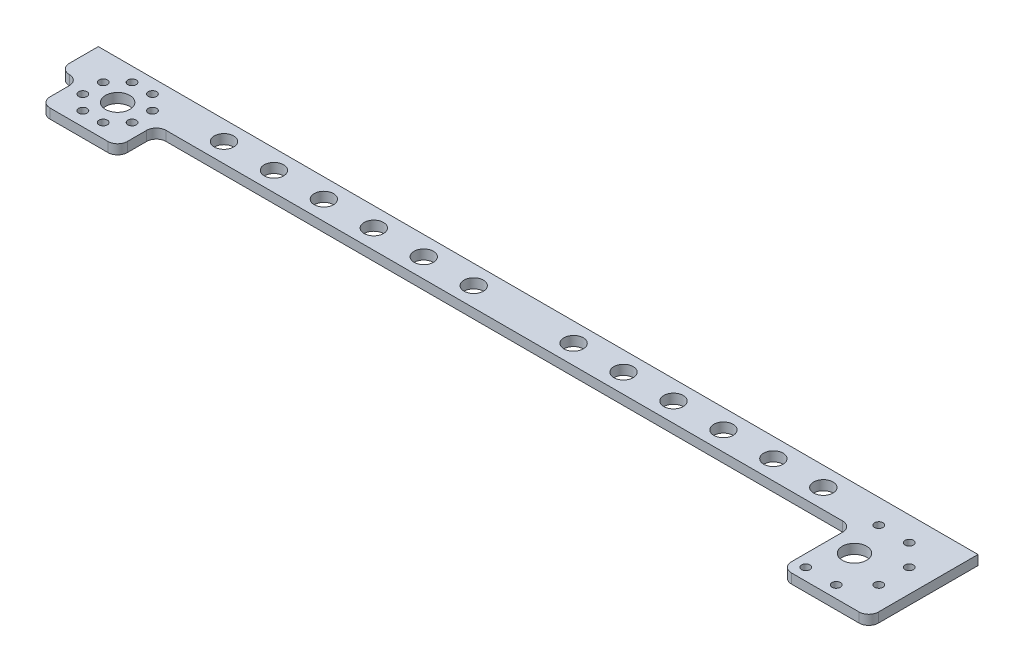
SolidWorks part; units mm, degrees
ref_plane "Front Plane" through (0, 0, 0) normal (0, 0, 1) x (1, 0, 0)
ref_plane "Top Plane" through (0, 0, 0) normal (0, 1, 0) x (1, 0, 0)
ref_plane "Right Plane" through (0, 0, 0) normal (1, 0, 0) x (0, 0, -1)
sketch "Sketch1" plane through (0, 0, 0) normal (0, 1, 0) x (1, 0, 0)
  line L1 (-228.6, 12.7) -> (228.6, 12.7)
  line L2 (-228.6, 12.7) -> (-228.6, -12.7) construction
  line L3 (-228.6, -12.7) -> (228.6, -12.7)
  line L4 (228.6, 12.7) -> (228.6, -12.7) construction
  line L5 (-228.6, 12.7) -> (228.6, -12.7) construction
  line L6 (-228.6, -12.7) -> (228.6, 12.7) construction
  line L7 (-228.6, 12.7) -> (-279.4, 12.7)
  line L8 (-279.4, 12.7) -> (-279.4, -38.1) construction
  line L9 (-279.4, -38.1) -> (-228.6, -38.1)
  line L10 (-228.6, -38.1) -> (-228.6, -12.7)
  line L11 (-279.4, 12.7) -> (-292.1, 12.7)
  line L12 (-292.1, 12.7) -> (-292.1, -12.7)
  line L13 (-292.1, -12.7) -> (-279.4, -12.7)
  line L14 (-279.4, -12.7) -> (-279.4, -38.1)
  line L15 (228.6, 12.7) -> (285.75, 12.7)
  line L16 (285.75, 12.7) -> (285.75, -59.055)
  line L17 (285.75, -59.055) -> (228.6, -59.055)
  line L18 (228.6, -59.055) -> (228.6, -12.7)
  point P0 (0, 0)
  dimension "D1" = 25.4
  dimension "D2" = 457.2
  dimension "D3" = 50.8
  dimension "D4" = 50.8
  dimension "D5" = 12.7
  dimension "D6" = 57.15
  dimension "D7" = 46.355
extrude "Boss-Extrude1" add sketch "Sketch1" along normal blind 6.35 contours L1 L15 L16 L17 L18 L3 L10 L9 L14 L13 L12 L11 L7
hole_wizard "M5 Clearance Hole1" positions "Sketch2" profile "Sketch3" hole size "M5" standard "ANSI Metric"
sketch "Sketch2" plane through (0, 6.35, 0) normal (0, 1, 0) x (1, 0, 0)
  line L0 (-279.4, -38.1) -> (-228.6, -38.1) construction
  line L15 (-270.1679, -19.397) -> (-270.1679, -6.003) construction
  line L16 (-270.1679, -6.003) -> (-260.697, 3.4679) construction
  line L17 (-260.697, 3.4679) -> (-247.303, 3.4679) construction
  line L18 (-247.303, 3.4679) -> (-237.8321, -6.003) construction
  line L19 (-237.8321, -6.003) -> (-237.8321, -19.397) construction
  line L20 (-237.8321, -19.397) -> (-247.303, -28.8679) construction
  line L21 (-247.303, -28.8679) -> (-260.697, -28.8679) construction
  line L22 (-260.697, -28.8679) -> (-270.1679, -19.397) construction
  circle A0 centre (-254, -12.7) radius 17.5 construction
  point P23 (-254, -38.1)
  point P37 (-260.697, -28.8679)
  point P41 (-237.8321, -19.397)
  point P67 (-260.697, 3.4679)
  point P69 (-247.303, 3.4679)
  point P71 (-237.8321, -6.003)
  point P84 (-270.1679, -19.397)
  point P107 (-247.303, -28.8679)
  point P110 (-270.1679, -6.003)
  dimension "D1" = 35
  dimension "D2" = 135
  dimension "D3" = 135
  dimension "D4" = 135
  dimension "D5" = 135
  dimension "D6" = 135
  dimension "D7" = 135
sketch "Sketch3" plane through (-270.1679, 6.35, 6.003) normal (1, 0, 0) x (0, 0, 1)
  line L0 (0, 0) -> (0, 14.3524)
  line L1 (0, 14.3524) -> (2.75, 12.7)
  line L2 (2.75, 12.7) -> (2.75, 0)
  line L5 (2.75, 0) -> (0, 0)
  line L10 (0, 14.3524) -> (-2.75, 12.7) construction
  line L11 (0, -6.35) -> (0, 107.95) construction
  dimension "Hole Dia." = 5.5
  dimension "Hole Depth" = 12.7
  dimension "Drill Angle" = 118
hole_wizard "#6 Clearance Hole2" positions "Sketch6" profile "Sketch7" hole size "#6" standard "ANSI Inch"
sketch "Sketch6" plane through (0, 0, -12.7) normal (0, 0, -1) x (-1, 0, 0)
  line L0 (215.9, 3.175) -> (-215.9, 3.175) construction
  line L2 (292.1, 0) -> (-285.75, 0) construction
  line L4 (292.1, 6.35) -> (292.1, 0) construction
  line L5 (-228.6, 6.35) -> (-228.6, 0) construction
  line L6 (-285.75, 6.35) -> (-285.75, 0) construction
  point P0 (279.4, 3.175)
  point P2 (215.9, 3.175)
  point P4 (0, 3.175)
  point P6 (-215.9, 3.175)
  point P14 (0, 3.175)
  point P26 (-276.225, 3.175)
  dimension "D1" = 3.175
  dimension "D2" = 12.7
  dimension "D3" = 12.7
  dimension "D4" = 12.7
  dimension "D5" = 9.525
sketch "Sketch7" plane through (-279.4, 3.175, -12.7) normal (1, 0, 0) x (0, 1, 0)
  line L0 (0, 0) -> (0, 13.8408)
  line L1 (0, 13.8408) -> (1.8986, 12.7)
  line L2 (1.8986, 12.7) -> (1.8986, 0)
  line L5 (1.8986, 0) -> (0, 0)
  line L10 (0, 13.8408) -> (-1.8986, 12.7) construction
  line L11 (0, -6.35) -> (0, 107.95) construction
  dimension "Hole Dia." = 3.7973
  dimension "Hole Depth" = 12.7
  dimension "Drill Angle" = 118
hole_wizard "M5 Clearance Hole2" positions "Sketch9" profile "Sketch10" hole size "M5" standard "ANSI Metric"
sketch "Sketch9" plane through (0, 6.35, 0) normal (0, 1, 0) x (1, 0, 0)
  line L1 (218.475, -17.175) -> (218.475, -37.175) construction
  line L3 (285.75, 12.7) -> (-292.1, 12.7) construction
  line L6 (228.6, -59.055) -> (228.6, -12.7) construction
  point P0 (218.475, -17.175)
  point P3 (218.475, -37.175)
  point P16 (244.475, -27.175)
  point P20 (256.475, -3.175)
  point P22 (256.475, -51.175)
  point P26 (236.475, -3.175)
  point P28 (236.475, -51.175)
  point P40 (218.475, -27.175)
  point P48 (270.475, -17.175)
  point P50 (270.475, -37.175)
  dimension "D1" = 15.875
  dimension "D2" = 20
  dimension "D3" = 15.875
  dimension "D4" = 26
  dimension "D5" = 8
  dimension "D6" = 24
  dimension "D7" = 48
  dimension "D8" = 20
  dimension "D9" = 26
sketch "Sketch10" plane through (218.475, 6.35, 17.175) normal (1, 0, 0) x (0, 0, 1)
  line L0 (0, 0) -> (0, 14.3524)
  line L1 (0, 14.3524) -> (2.75, 12.7)
  line L2 (2.75, 12.7) -> (2.75, 0)
  line L5 (2.75, 0) -> (0, 0)
  line L10 (0, 14.3524) -> (-2.75, 12.7) construction
  line L11 (0, -6.35) -> (0, 107.95) construction
  dimension "Hole Dia." = 5.5
  dimension "Hole Depth" = 12.7
  dimension "Drill Angle" = 118
fillet "Fillet1" radius 6.35 8 edges at (-228.6, 3.175, 38.1) (-228.6, 3.175, 12.7) (-292.1, 3.175, 12.7) (-279.4, 3.175, 38.1) (-279.4, 3.175, 12.7) (285.75, 3.175, 59.055) (228.6, 3.175, 59.055) (228.6, 3.175, 12.7)
sketch "Sketch8" plane through (0, 6.35, 0) normal (0, 1, 0) x (1, 0, 0)
  line L0 (285.75, 12.7) -> (-292.1, 12.7) construction
  line L1 (-196.85, 0) -> (-164.0417, 0) construction
  line L2 (-164.0417, 0) -> (-131.2333, 0) construction
  line L3 (-131.2333, 0) -> (-98.425, 0) construction
  line L4 (-98.425, 0) -> (-65.6167, 0) construction
  line L5 (-65.6167, 0) -> (-32.8083, 0) construction
  line L6 (-32.8083, 0) -> (0, 0) construction
  line L8 (-228.6, -31.75) -> (-228.6, -19.05) construction
  circle A0 centre (-254, -12.7) radius 8
  circle A1 centre (244.475, -27.175) radius 8
  circle A2 centre (-196.85, 0) radius 6.35 construction
  circle A3 centre (-164.0417, 0) radius 6.35 construction
  circle A4 centre (-131.2333, 0) radius 6.35 construction
  circle A5 centre (-65.6167, 0) radius 6.35 construction
  circle A6 centre (-32.8083, 0) radius 6.35 construction
  circle A7 centre (-98.425, 0) radius 6.35 construction
  dimension "D1" = 16
  dimension "D2" = 16
  dimension "D4" = 12.7
  dimension "D3" = 12.7
  dimension "D5" = 31.75
  dimension "D6" = 228.6
extrude "Cut-Extrude1" cut sketch "Sketch8" against normal blind 6.35
sketch "Sketch11" plane through (0, 6.35, 0) normal (0, 1, 0) x (1, 0, 0)
  circle A0 centre (-196.85, 0) radius 6.35
  circle A1 centre (-164.0417, 0) radius 6.35
  circle A2 centre (-131.2333, 0) radius 6.35
  circle A3 centre (-98.425, 0) radius 6.35
  circle A4 centre (-65.6167, 0) radius 6.35
  circle A5 centre (-32.8083, 0) radius 6.35
  dimension "D1" = 12.7
extrude "Cut-Extrude2" cut sketch "Sketch11" against normal blind 6.35
mirror "Mirror1" about plane through (0, 0, 0) normal (1, 0, 0) of "Cut-Extrude2"
